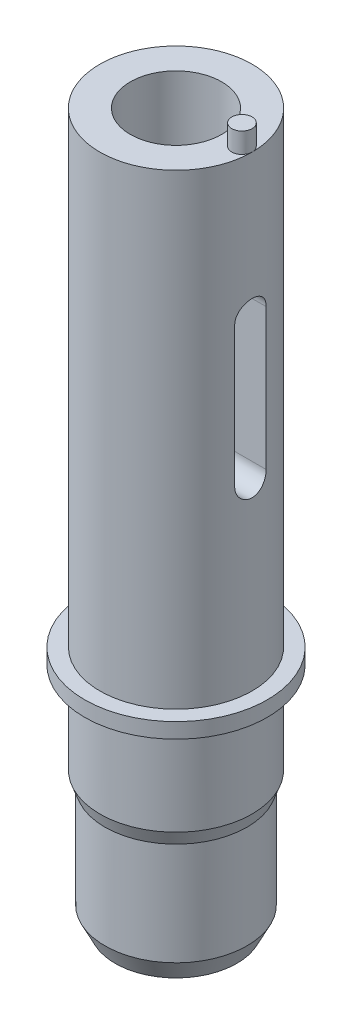
SolidWorks part; units mm, degrees
ref_plane "Front" through (0, 0, 0) normal (0, 0, 1) x (1, 0, 0)
ref_plane "Top" through (0, 0, 0) normal (0, 1, 0) x (1, 0, 0)
ref_plane "Right" through (0, 0, 0) normal (1, 0, 0) x (0, 0, -1)
sketch "Sketch1" plane through (0, 0, 0) normal (0, 0, 1) x (1, 0, 0)
  line L0 (0, -80.7849) -> (0, 12.9711) construction
  line L1 (7.5, 0) -> (7.5, -46)
  line L2 (3.35, -70) -> (7, -70)
  line L3 (3.35, -70) -> (3.35, 0)
  line L4 (3.35, 0) -> (7.5, 0)
  line L5 (9, -47.5) -> (9, -46)
  line L6 (7.5, -46) -> (9, -46)
  line L7 (9, -47.5) -> (7.5, -47.5)
  line L8 (7.5, -47.5) -> (7.5, -56.5)
  line L9 (7.5, -56.5) -> (7, -56.5)
  line L10 (7, -56.5) -> (7, -70)
  dimension "D1" = 18
  dimension "D2" = 6.7
  dimension "D3" = 70
  dimension "D4" = 14
  dimension "D5" = 15
  dimension "D6" = 13.5
  dimension "D7" = 22.5
  dimension "D8" = 1.5
revolve "Revolve1" add sketch "Sketch1" angle 360 about L0
sketch "Sketch6" plane through (0, 0, 0) normal (0, 1, 0) x (1, 0, 0)
  circle A0 centre (6.499, 0) radius 1
  dimension "D1" = 2
  dimension "D2" = 6.499
extrude "Boss-Extrude1" add sketch "Sketch6" along normal blind 2
sketch "Sketch2" plane through (0, 0, 0) normal (0, 0, 1) x (1, 0, 0)
  line L0 (0, -73.382) -> (0, 4.1105) construction
  line L1 (9, 0) -> (-9, 0) construction
  line L2 (-3.35, 0) -> (-4.25, 0)
  line L3 (-3.35, 0) -> (-3.35, -40)
  line L4 (-4.25, -30) -> (-4, -30)
  line L5 (-4.25, 0) -> (-4.25, -30)
  line L6 (-3.35, 0) -> (-3.35, -70) construction
  line L7 (-4, -30) -> (-4, -40)
  line L8 (-4, -40) -> (-3.35, -40)
  dimension "D1" = 40
  dimension "D2" = 8.5
  dimension "D3" = 30
  dimension "D4" = 8
revolve "Cut-Revolve1" cut sketch "Sketch2" angle 360 about L0
sketch "Sketch3" plane through (0, 0, 0) normal (1, 0, 0) x (0, 0, -1)
  line L0 (0, -27.95) -> (0, -14.05) construction
  line L1 (-1.55, -27.95) -> (-1.55, -14.05)
  line L2 (1.55, -27.95) -> (1.55, -14.05)
  arc A0 (-1.55, -27.95) -> (1.55, -27.95) centre (0, -27.95) ccw
  arc A1 (1.55, -14.05) -> (-1.55, -14.05) centre (0, -14.05) ccw
  point P3 (0, -21)
  dimension "D3" = 17
  dimension "D1" = 3.1
  dimension "D2" = 12.5
extrude "Cut-Extrude1" cut sketch "Sketch3" against normal through all and the other way through all
hole_wizard "M10x1.0 Tapped Hole1" positions "Sketch5" profile "Sketch4" tap size "M10x1.0" standard "JIS"
sketch "Sketch5" plane through (0, 0, 0) normal (0, 1, 0) x (-1, 0, 0)
  point P0 (0, 0)
sketch "Sketch4" plane through (0, 0, 0) normal (1, 0, 0) x (0, 0, 1)
  line L0 (0, 0) -> (0, 11.7039)
  line L1 (0, 11.7039) -> (4.5, 9)
  line L2 (4.5, 9) -> (4.5, 0)
  line L5 (4.5, 0) -> (0, 0)
  line L10 (0, 11.7039) -> (-4.5, 9) construction
  line L11 (0, -6.35) -> (0, 107.95) construction
  dimension "Tap Drill Dia." = 9
  dimension "Tap Drill Depth" = 9
  dimension "Drill Angle" = 118
cosmetic thread "Hole Thread1" parameters "D1"=7, "D2"=10
chamfer "Chamfer1" distance 2 distance2 1 1 edges at (0, -70, -7) first distance on face at (0, -56.5, -7)
chamfer "Chamfer2" distance 0.5 angle 70 1 edges at (0, -56.5, -7) first distance on face at (0, -56.5, -7.5)
